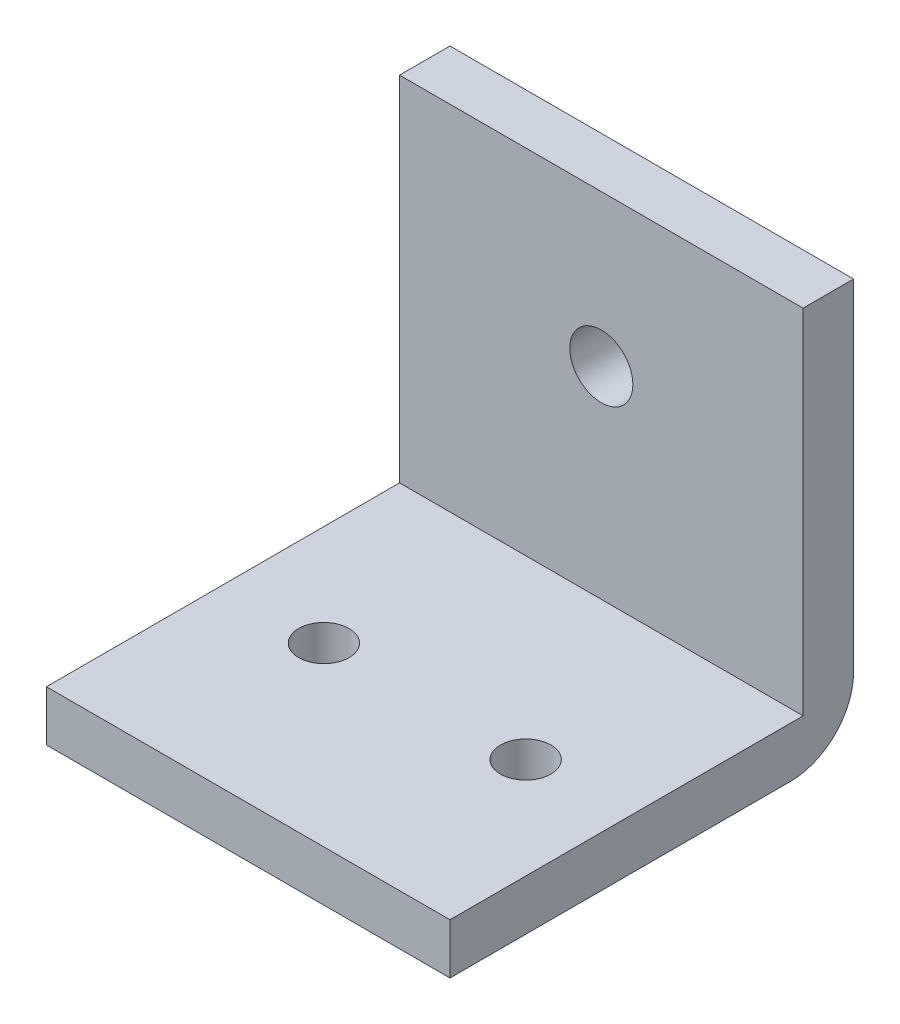
SolidWorks part; units mm, degrees
ref_plane "Front Plane" through (0, 0, 0) normal (0, 0, 1) x (1, 0, 0)
ref_plane "Top Plane" through (0, 0, 0) normal (0, 1, 0) x (1, 0, 0)
ref_plane "Right Plane" through (0, 0, 0) normal (1, 0, 0) x (0, 0, -1)
sketch "Sketch1" plane through (0, 0, 0) normal (0, 0, 1) x (1, 0, 0)
  line L0 (20, 25) -> (20, 40) construction
  line L1 (0, 0) -> (40, 0)
  line L2 (0, 0) -> (0, 40)
  line L3 (0, 40) -> (40, 40)
  line L4 (40, 0) -> (40, 40)
  line L6 (0, 0) -> (40, 0)
  line L7 (0, 0) -> (0, 5)
  line L8 (0, 5) -> (40, 5)
  line L9 (40, 0) -> (40, 5)
  circle A0 centre (20, 25) radius 3.125
  dimension "D3" = 6.25
  dimension "D4" = 15
  dimension "D1" = 40
  dimension "D2" = 40
  dimension "D5" = 5
extrude "Boss-Extrude1" add sketch "Sketch1" along normal blind 5 contours A0 L3 L2 L8 L4 region at (0.5315, 22.5, 0)
extrude "Boss-Extrude2" add sketch "Sketch1<3>" along normal blind 40 contours L8 L2 L1 L4 region at (20, 2.5, 0)
sketch "Sketch1<3>" plane through (0, 0, 0) normal (0, 0, 1) x (1, 0, 0) same geometry as "Sketch1"
fillet "Fillet1" radius 6.25 1 edges at (20, 0, 0)
sketch "Sketch2" plane through (0, 5, 0) normal (0, 1, 0) x (1, 0, 0)
  line L0 (0, -22.5) -> (40, -22.5) construction
  line L1 (0, -40) -> (0, -5) construction
  line L2 (40, -40) -> (40, -5) construction
  line L3 (20, -22.5) -> (20, -29.0805) construction
  circle A0 centre (10, -22.5) radius 2.5
  circle A1 centre (30, -22.5) radius 2.5
  dimension "D1" = 5
  dimension "D2" = 10
extrude "Cut-Extrude1" cut sketch "Sketch2" against normal through all
